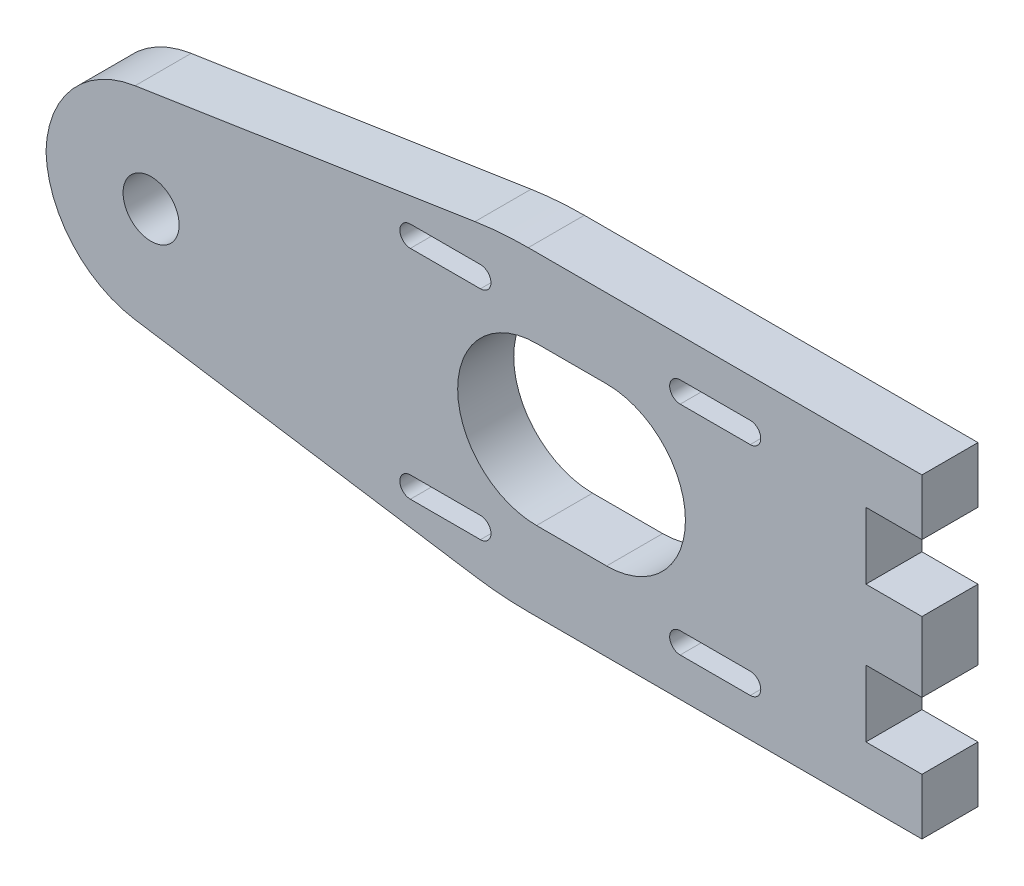
SolidWorks part; units mm, degrees
ref_plane "Front Plane" through (0, 0, 0) normal (0, 0, 1) x (1, 0, 0)
ref_plane "Top Plane" through (0, 0, 0) normal (0, 1, 0) x (1, 0, 0)
ref_plane "Right Plane" through (0, 0, 0) normal (1, 0, 0) x (0, 0, -1)
sketch "Sketch1" plane through (0, 0, 0) normal (0, 0, 1) x (1, 0, 0)
  line L0 (0, 22.5) -> (0, 27.5)
  line L1 (0, 0) -> (-125, 0)
  line L2 (0, 0) -> (0, 45)
  line L3 (0, 45) -> (-125, 45)
  line L4 (-125, 0) -> (-125, 45)
  line L5 (0, 45) -> (-8, 45)
  line L6 (0, 45) -> (0, 37)
  line L7 (0, 37) -> (-8, 37)
  line L8 (-8, 45) -> (-8, 37)
  line L9 (0, 0) -> (-8, 0)
  line L10 (0, 0) -> (0, 8)
  line L11 (0, 8) -> (-8, 8)
  line L12 (-8, 0) -> (-8, 8)
  line L13 (0, 27.5) -> (-8, 27.5)
  line L14 (-8, 27.5) -> (-8, 17.5)
  line L15 (-8, 17.5) -> (0, 17.5)
  line L16 (0, 17.5) -> (0, 22.5)
  line L17 (-125, 22.5) -> (-105, 22.5)
  line L18 (-105, 22.5) -> (-110, 22.5)
  line L19 (-110, 22.5) -> (-10, 22.5)
  line L21 (-8, 8) -> (-8, 17.5)
  line L30 (-75, 18.5) -> (-85, 18.5)
  line L31 (-75, 18.5) -> (-75, 26.5)
  line L32 (-8, 17.5) -> (-8, 37)
  line L33 (-75, 26.5) -> (-85, 26.5)
  line L34 (-85, 18.5) -> (-85, 26.5)
  line L35 (-75, 18.5) -> (-85, 26.5) construction
  line L36 (-75, 26.5) -> (-85, 18.5) construction
  dimension "D1" = 125
  dimension "D2" = 45
  dimension "D3" = 5
  dimension "D4" = 10
  dimension "D5" = 8
  dimension "D6" = 8
  dimension "D7" = 8
extrude "Boss-Extrude1" add sketch "Sketch1" along normal blind 8 contours L12 L1 L2 L11 | L14 L15 L2 L0 L13 | L3 L8 L7 L2 | L31 L4 L1 L12 L21 L14 L32 L8 L3 | L34 L19 L31 L33 | L34 L30 L31 L19 region at (-4, 22.5, 0) region at (-4, 41, 0) region at (-80, 24.5, 0) region at (-80, 20.5, 0) region at (-9.2536, 22.5, 0) region at (-4, 4, 0)
chamfer "Chamfer1" distance 10 distance2 65 1 edges at (-125, 0, 4) first distance on face at (-125, 22.5, 4)
chamfer "Chamfer2" distance 65 distance2 10 1 edges at (-125, 45, 4) first distance on face at (-62.5, 45, 4)
fillet "Fillet2" radius 15 2 edges at (-125, 10, 4) (-125, 35, 4)
fillet "Fillet3" radius 50 2 edges at (-60, 0, 4) (-60, 45, 4)
sketch "Sketch2" plane through (0, 0, 8) normal (0, 0, 1) x (1, 0, 0)
  circle A0 centre (-110, 22.8688) radius 4
extrude "Cut-Extrude1" cut sketch "Sketch2" against normal blind 80
sketch "Sketch3" plane through (0, 0, 8) normal (0, 0, 1) x (1, 0, 0)
  line L0 (-8, 17.5) -> (-8, 27.5)
  line L1 (-8, 22.5) -> (-50, 22.5)
  line L2 (-50, 22.5) -> (-50, 38)
  line L3 (-50, 38) -> (-50, 22.5)
  line L4 (-45, 22.5) -> (-55, 22.5) construction
  line L5 (-73, 38) -> (-63, 38) construction
  line L6 (-45, 11.25) -> (-55, 11.25)
  line L7 (-45, 33.75) -> (-55, 33.75)
  line L8 (-34.5, 38) -> (-24.5, 38) construction
  line L9 (-73, 39.5) -> (-63, 39.5)
  line L10 (-34.5, 39.5) -> (-24.5, 39.5)
  line L11 (-34.5, 36.5) -> (-24.5, 36.5)
  line L12 (-73, 36.5) -> (-63, 36.5)
  line L13 (-73, 7) -> (-63, 7) construction
  line L14 (-73, 8.5) -> (-63, 8.5)
  line L15 (-73, 5.5) -> (-63, 5.5)
  line L16 (-34.5, 7) -> (-24.5, 7) construction
  line L17 (-34.5, 8.5) -> (-24.5, 8.5)
  line L18 (-34.5, 5.5) -> (-24.5, 5.5)
  arc A0 (-45, 11.25) -> (-45, 33.75) centre (-45, 22.5) ccw
  arc A1 (-55, 33.75) -> (-55, 11.25) centre (-55, 22.5) ccw
  arc A2 (-34.5, 39.5) -> (-34.5, 36.5) centre (-34.5, 38) ccw
  arc A3 (-24.5, 36.5) -> (-24.5, 39.5) centre (-24.5, 38) ccw
  arc A4 (-73, 39.5) -> (-73, 36.5) centre (-73, 38) ccw
  arc A5 (-63, 36.5) -> (-63, 39.5) centre (-63, 38) ccw
  arc A6 (-73, 8.5) -> (-73, 5.5) centre (-73, 7) ccw
  arc A7 (-63, 5.5) -> (-63, 8.5) centre (-63, 7) ccw
  arc A8 (-34.5, 8.5) -> (-34.5, 5.5) centre (-34.5, 7) ccw
  arc A9 (-24.5, 5.5) -> (-24.5, 8.5) centre (-24.5, 7) ccw
  point P11 (-50, 22.5)
  point P20 (-29.5, 38)
  point P26 (-68, 38)
  point P33 (-68, 7)
  point P40 (-29.5, 7)
  dimension "D3" = 11.25
  dimension "D1" = 42
  dimension "D2" = 15.5
  dimension "D4" = 5
  dimension "D5" = 20.5
  dimension "D6" = 15.5
  dimension "D9" = 5
  dimension "D7" = 2
  dimension "D8" = 2
extrude "Cut-Extrude2" cut sketch "Sketch3" against normal blind 8 contours L15 A7 L14 A6 | L12 A5 L9 A4 | L7 A1 L6 A0 L1 L2 | L1 A0 L7 L2 | L11 A3 L10 A2 | L18 A9 L17 A8 region at (-52.3819, 20.806, 8) region at (-42.8543, 27.582, 8) region at (-68, 38, 8) region at (-29.5, 38, 8) region at (-68, 7, 8) region at (-29.5, 7, 8)
